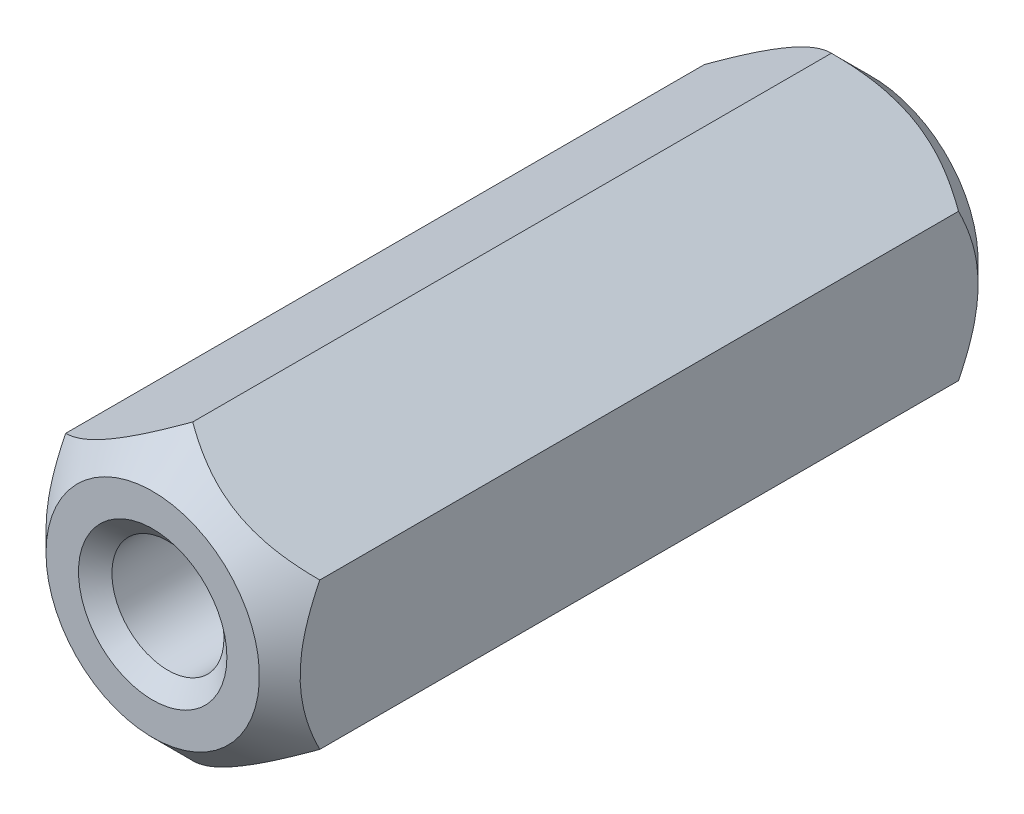
SolidWorks part; units mm, degrees
ref_plane "Front Plane" through (0, 0, 0) normal (0, 0, 1) x (1, 0, 0)
ref_plane "Top Plane" through (0, 0, 0) normal (0, 1, 0) x (1, 0, 0)
ref_plane "Right Plane" through (0, 0, 0) normal (1, 0, 0) x (0, 0, -1)
sketch "Sketch1" plane through (0, 0, 0) normal (0, 0, 1) x (1, 0, 0)
  line L1 (3.175, -1.8331) -> (3.175, 1.8331)
  line L2 (3.175, 1.8331) -> (0, 3.6662)
  line L3 (0, 3.6662) -> (-3.175, 1.8331)
  line L4 (-3.175, 1.8331) -> (-3.175, -1.8331)
  line L5 (-3.175, -1.8331) -> (0, -3.6662)
  line L6 (0, -3.6662) -> (3.175, -1.8331)
  circle A0 centre (0, 0) radius 3.175 construction
  dimension "D1" = 6.35
extrude "Boss-Extrude1" add sketch "Sketch1" along normal blind 8.98 and the other way blind 8.98
ref_axis "Axis1" through (0, 0, -0.635) along (0, 0, 1)
sketch "Sketch3" plane through (0, 0, 0) normal (1, 0, 0) x (0, 0, -1)
  line L0 (-8.98, 3.6662) -> (8.98, 3.6662) construction
  line L1 (-7.98, 3.6662) -> (-8.98, 2.6662)
  line L2 (-8.98, 1.8331) -> (-8.98, 3.6662) construction
  line L3 (-8.98, 2.6662) -> (-8.98, 3.6662)
  line L4 (-8.98, 3.6662) -> (-7.98, 3.6662)
  dimension "D1" = 1
  dimension "D2" = 45
revolve "Cut-Revolve2" cut sketch "Sketch3" angle 360 about axis through (0, 0, -0.635) along (0, 0, 1)
mirror "Mirror1" about plane through (0, 0, 0) normal (0, 0, 1) of "Cut-Revolve2"
hole_wizard "CSK for #1 Flat Head Machine Screw (100)1" positions "Sketch5" profile "Sketch4" countersink size "#1" standard "ANSI Inch" end condition through all
sketch "Sketch5" plane through (0, 0, 8.98) normal (0, 0, 1) x (1, 0, 0)
  point P0 (0, 0)
sketch "Sketch4" plane through (0, 0, 8.98) normal (1, 0, 0) x (0, -1, 0)
  line L0 (0, 0) -> (0, 17.96)
  line L1 (0, 17.96) -> (1.6637, 17.96)
  line L2 (1.4, 17.6963) -> (1.4, 0.3811)
  line L3 (1.4, 0.3811) -> (1.8542, 0)
  line L5 (1.8542, 0) -> (0, 0)
  line L6 (-1.4, 0.3811) -> (-1.8542, 0) construction
  line L7 (1.6637, 17.96) -> (1.4, 17.6963)
  line L8 (-1.6637, 17.96) -> (-1.4, 17.6963) construction
  line L11 (0, -6.35) -> (0, 107.95) construction
  dimension "Thru Hole Dia." = 2.8
  dimension "Thru Hole Depth" = 17.96
  dimension "Near C'Sink Dia." = 3.7084
  dimension "Near C'Sink Angle" = 100
  dimension "Far C'Sink Dia." = 3.3274
  dimension "Far C'Sink Angle" = 90
